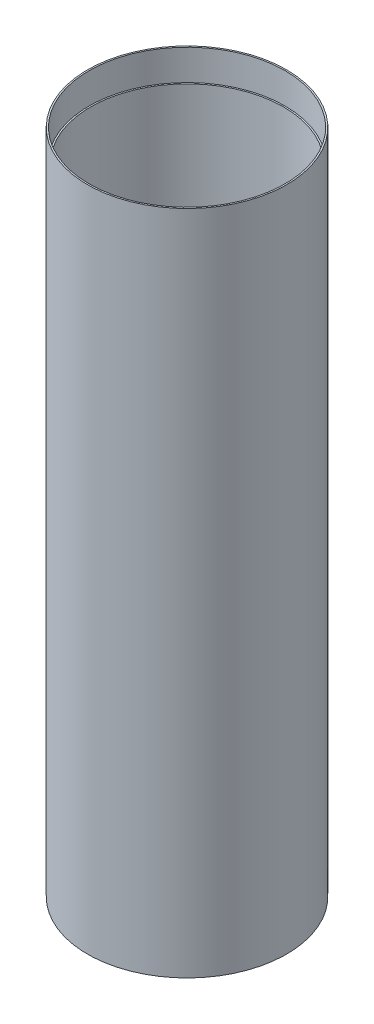
SolidWorks part; units mm, degrees
material "HYPALON"
ref_plane "Płaszczyzna przednia" through (0, 0, 0) normal (0, 0, 1) x (1, 0, 0)
ref_plane "Płaszczyzna górna" through (0, 0, 0) normal (0, 1, 0) x (1, 0, 0)
ref_plane "Płaszczyzna prawa" through (0, 0, 0) normal (1, 0, 0) x (0, 0, -1)
sketch "Szkic1" plane through (0, 0, 0) normal (0, 0, 1) x (1, 0, 0)
  line L0 (64, 217.5) -> (65, 217.5)
  line L1 (65, 217.5) -> (65, -217.5)
  line L2 (65, -217.5) -> (64, -217.5)
  line L3 (64, -217.5) -> (64, -197.5)
  line L4 (64, -197.5) -> (63, -197.5)
  line L5 (63, -197.5) -> (63, 197.5)
  line L6 (63, 197.5) -> (64, 197.5)
  line L7 (64, 197.5) -> (64, 217.5)
  line L8 (0, 0) -> (0, 92.2309) construction
  point P2 (63, 0)
  dimension "D1" = 435
  dimension "D2" = 20
  dimension "D3" = 20
  dimension "D4" = 2
  dimension "D5" = 63
  dimension "3" = 1
revolve "Obrót1" add sketch "Szkic1" angle 360 about L8
